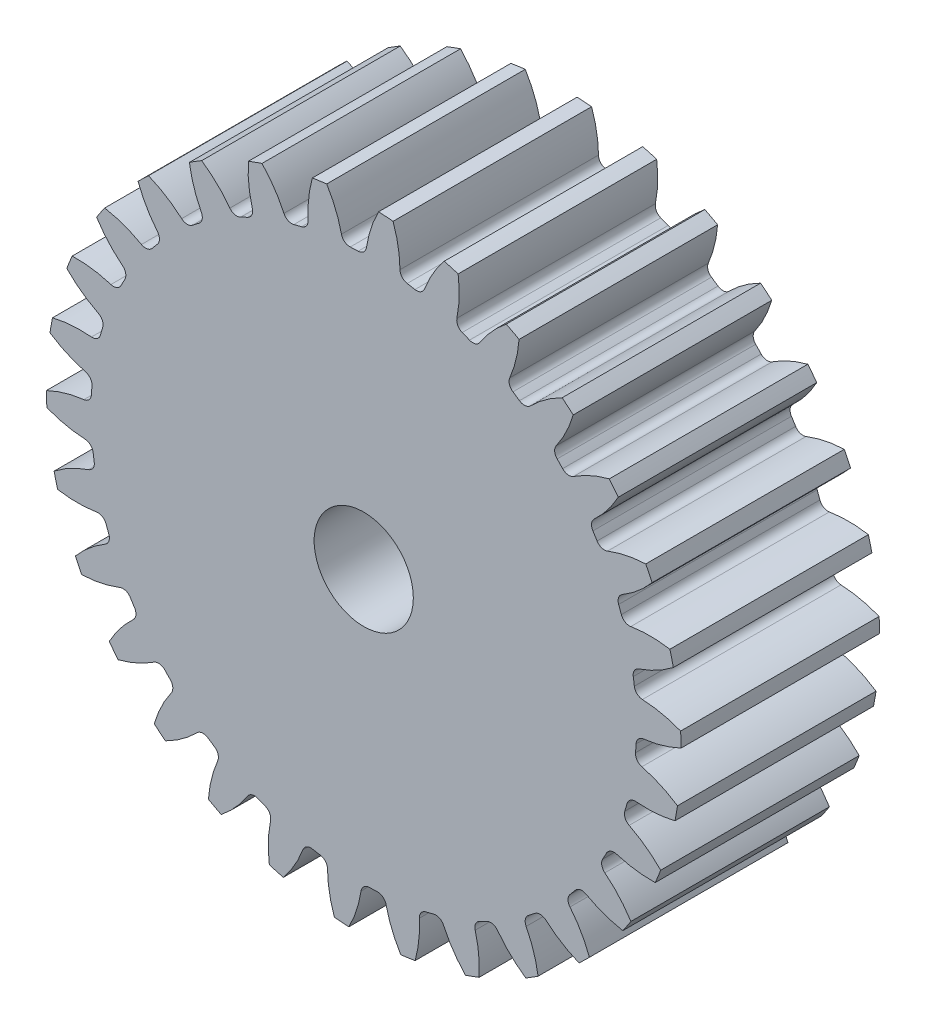
SolidWorks part; units mm, degrees
ref_plane "Front" through (0, 0, 0) normal (0, 0, 1) x (1, 0, 0)
ref_plane "Top" through (0, 0, 0) normal (0, 1, 0) x (1, 0, 0)
ref_plane "Right" through (0, 0, 0) normal (1, 0, 0) x (0, 0, -1)
sketch "Sketch3" plane through (0, 0, 0) normal (0, 0, 1) x (1, 0, 0)
  circle A0 centre (0, 0) radius 16
  dimension "od" = 32
extrude "gearBody" add sketch "Sketch3" along normal blind 10.0076
sketch "Sketch2" plane through (0, 0, 0) normal (0, 0, 1) x (1, 0, 0)
  line L0 (0, 0) -> (13.4168, 5.5574) construction
  line L1 (17.85, -4.7288) -> (0, 0) construction
  line L2 (0, 0) -> (36.3143, 0) construction
  line L3 (14.9989, -0.1803) -> (14.8786, -1.9047) construction
  line L5 (14.9387, -1.0425) -> (0, 0) construction
  line L7 (0, 0) -> (14.5222, 0) construction
  arc A0 (14.5193, -0.2915) -> (14.419, -1.728) centre (0, 0) ccw construction
  arc A1 (15.9988, 0.1948) -> (15.8167, -2.4151) centre (0, 0) ccw construction
  arc A2 (14.9989, -0.1803) -> (14.8786, -1.9047) centre (0, 0) ccw construction
  arc A3 (13.7005, -1.1556) -> (13.7283, -0.7585) centre (0, 0) ccw
  arc A4 (17.85, -4.7288) -> (14.021, -1.609) centre (12.5148, -7.3671) ccw
  arc A5 (17.85, -4.7288) -> (18.3338, 2.2037) centre (0, 0) ccw
  arc A6 (18.3338, 2.2037) -> (14.1086, -0.3541) centre (13.4168, 5.5574) cw
  arc A7 (13.7283, -0.7585) -> (14.1086, -0.3541) centre (14.1587, -0.7823) cw
  arc A8 (14.021, -1.609) -> (13.7005, -1.1556) centre (14.1301, -1.1919) cw
  point P6 (18.3338, 2.2037)
  point P22 (17.85, -4.7288)
  dimension "baseDia" = 29.0444
  dimension "od" = 32
  dimension "pd" = 30
  dimension "rd" = 27.4984
  dimension "rFillet" = 0.4311
  dimension "pointX" = 18.3338
  dimension "pointY" = 2.2037
  dimension "CTT" = 1.7244
  dimension "flankCenterAngle" = 22.5
extrude "toothCut" cut sketch "Sketch2" along normal through all
pattern_circular "CirPattern1" count 30 over 360 about axis through (0, 0, 10.0076) along (0, 0, -1) of "toothCut"
ref_axis "toothSpace" through (0, 0, 0) along (0.9976, -0.0696, 0)
ref_axis "Axis2" through (15.7573, -2.7762, 0) along (-0.9848, 0.1735, 0)
sketch "hub1Dia" plane through (0, 0, 0) normal (0, 0, -1) x (-1, 0, 0)
  circle A0 centre (0, 0) radius 5
  dimension "hub1Dia" = 10
extrude "hub1" add sketch "hub1Dia" along normal blind 5
sketch "hub2Dia" plane through (0, 0, 10.0076) normal (0, 0, 1) x (1, 0, 0)
  circle A0 centre (0, 0) radius 0.5
  dimension "hub2dia" = 1
sketch "boreDia" plane through (0, 0, 0) normal (0, 0, 1) x (1, 0, 0)
  circle A0 centre (0, 0) radius 2.5
  dimension "boreDia" = 5
extrude "bore" cut sketch "boreDia" against normal mid plane 25400
sketch "kwy1sketch" plane through (0, 0, 0) normal (0, 0, 1) x (1, 0, 0)
  line L0 (-5.3271, 0.7479) -> (0, 0) construction
  line L1 (3.5355, 0.0085) -> (3.3965, -0.9818)
  line L2 (3.3965, -0.9818) -> (2.1586, -0.808)
  line L3 (3.5355, 0.0085) -> (2.2977, 0.1823)
  line L4 (2.1586, -0.808) -> (0, 0)
  line L5 (0, 0) -> (2.2977, 0.1823)
  line L6 (0, 0) -> (13.7158, -0.9572) construction
  line L7 (3.466, -0.4866) -> (0, 0) construction
  arc A7 (13.7005, -1.1556) -> (13.7283, -0.7585) centre (0, 0) ccw construction
  point P9 (3.466, -0.4866)
  point P13 (-0.8886, 0.1248)
  dimension "kwy1width" = 1
  dimension "kwy1depth" = 3.5
  dimension "kwy1angle" = 4
  dimension "kwy1Depth2" = 1.25
sketch "kwy2sketch" plane through (0, 0, 0) normal (0, 0, 1) x (1, 0, 0)
  line L0 (13.7158, -0.9572) -> (0, 0) construction
  line L1 (0, 0) -> (-2.9685, -2.2375) construction
  line L2 (2.494, 2.506) -> (3.0959, 1.7075)
  line L3 (3.0959, 1.7075) -> (2.0977, 0.9551)
  line L4 (2.494, 2.506) -> (1.4958, 1.7536)
  line L5 (2.0977, 0.9551) -> (0, 0)
  line L6 (0, 0) -> (1.4958, 1.7536)
  arc A2 (13.7005, -1.1556) -> (13.7283, -0.7585) centre (0, 0) ccw construction
  point P10 (2.7949, 2.1067)
  dimension "kwy2angle" = 41
  dimension "kwy2Width" = 1
  dimension "kwy2depth" = 3.5
  dimension "kwy2Depth2" = 1.25
sketch "kwy3sketch" plane through (0, 0, 0) normal (0, 0, 1) x (1, 0, 0)
  line L0 (13.7158, -0.9572) -> (0, 0) construction
  line L1 (0, 0) -> (-0.3739, -2.6632) construction
  line L2 (-0.0085, 3.5355) -> (0.9818, 3.3965)
  line L3 (0.9818, 3.3965) -> (0.808, 2.1586)
  line L4 (-0.0085, 3.5355) -> (-0.1823, 2.2977)
  line L5 (0.808, 2.1586) -> (0, 0)
  line L6 (-0.1823, 2.2977) -> (0, 0)
  point P10 (0.4866, 3.466)
  dimension "kwy3angle" = 86
  dimension "kwy3depth" = 3.5
  dimension "kwy3width" = 1
  dimension "kwy3Depth2" = 1.25
sketch "kwy4sketch" plane through (0, 0, 0) normal (0, 0, 1) x (1, 0, 0)
  line L0 (13.7158, -0.9572) -> (0, 0) construction
  line L1 (0, 0) -> (1.2657, -1.6792) construction
  line L2 (-1.7075, 3.0959) -> (-2.506, 2.494)
  line L3 (-2.506, 2.494) -> (-1.7536, 1.4958)
  line L4 (-1.7536, 1.4958) -> (0, 0)
  line L5 (-0.9551, 2.0977) -> (0, 0)
  line L6 (-1.7075, 3.0959) -> (-0.9551, 2.0977)
  point P15 (-2.1067, 2.7949)
  dimension "kwy4angle" = 131
  dimension "kwy4depth" = 3.5
  dimension "kwy4width" = 1
  dimension "kwy4Depth2" = 1.25
sketch "kwy5sketch" plane through (0, 0, 0) normal (0, 0, 1) x (1, 0, 0)
  line L0 (13.7158, -0.9572) -> (0, 0) construction
  line L1 (0, 0) -> (1.7884, -0.2511) construction
  line L2 (-3.3965, 0.9818) -> (-3.5355, -0.0085)
  line L3 (-3.5355, -0.0085) -> (-2.2977, -0.1823)
  line L4 (-3.3965, 0.9818) -> (-2.1586, 0.808)
  line L5 (-2.2977, -0.1823) -> (0, 0)
  line L6 (-2.1586, 0.808) -> (0, 0)
  point P10 (-3.466, 0.4866)
  dimension "kwy5width" = 1
  dimension "kwy5depth" = 3.5
  dimension "kwy5angle" = 176
  dimension "kwy5Depth2" = 1.25
sketch "kwy6sketch" plane through (0, 0, 0) normal (0, 0, 1) x (1, 0, 0)
  line L0 (13.7158, -0.9572) -> (0, 0) construction
  line L1 (0, 0) -> (1.441, 1.0862) construction
  line L2 (-3.0959, -1.7075) -> (-2.494, -2.506)
  line L3 (-2.494, -2.506) -> (-1.4958, -1.7536)
  line L4 (-3.0959, -1.7075) -> (-2.0977, -0.9551)
  line L5 (-1.4958, -1.7536) -> (0, 0)
  line L6 (-2.0977, -0.9551) -> (0, 0)
  point P10 (-2.7949, -2.1067)
  dimension "kwy6angle" = 221
  dimension "kwy6width" = 1
  dimension "kwy6depth" = 3.5
  dimension "kwy6Depth2" = 1.25
sketch "kwy7sketch" plane through (0, 0, 0) normal (0, 0, 1) x (1, 0, 0)
  line L0 (13.7158, -0.9572) -> (0, 0) construction
  line L1 (0, 0) -> (0.2811, 2.002) construction
  line L2 (-0.9818, -3.3965) -> (0.0085, -3.5355)
  line L3 (-0.9818, -3.3965) -> (-0.808, -2.1586)
  line L4 (0.0085, -3.5355) -> (0.1823, -2.2977)
  line L5 (-0.808, -2.1586) -> (0, 0)
  line L6 (0.1823, -2.2977) -> (0, 0)
  point P10 (-0.4866, -3.466)
  dimension "kwy7angle" = 86
  dimension "kwy7width" = 1
  dimension "kwy7depth" = 3.5
  dimension "kwy7angle1" = 266
  dimension "kwy7Depth2" = 1.25
sketch "kwy8sketch" plane through (0, 0, 0) normal (0, 0, 1) x (1, 0, 0)
  line L0 (13.7158, -0.9572) -> (0, 0) construction
  line L1 (0, 0) -> (-1.0811, 1.4343) construction
  line L2 (1.7075, -3.0959) -> (2.506, -2.494)
  line L3 (2.506, -2.494) -> (1.7536, -1.4958)
  line L4 (1.7075, -3.0959) -> (0.9551, -2.0977)
  line L5 (1.7536, -1.4958) -> (0, 0)
  line L6 (0.9551, -2.0977) -> (0, 0)
  point P10 (2.1067, -2.7949)
  dimension "kwy8angle" = 311
  dimension "kwy8width" = 1
  dimension "kwy8depth" = 3.5
  dimension "kwy8Depth2" = 1.25
sketch "centerLine" plane through (0, 0, 0) normal (0, 1, 0) x (1, 0, 0)
  line L0 (0, 36.4807) -> (0, -59.6309) construction
ref_plane "CB1plane" through (0, 0, -5) normal (0, 0, -1) x (-1, 0, 0)
sketch "CB1diameter" plane through (0, 0, -5) normal (0, 0, -1) x (-1, 0, 0)
  circle A0 centre (0, 0) radius 0.5
  dimension "CB1diameter" = 1
ref_plane "CB2plane" through (0, 0, 10.0076) normal (0, 0, 1) x (1, 0, 0)
sketch "CB2diameter" plane through (0, 0, 10.0076) normal (0, 0, 1) x (1, 0, 0)
  circle A0 centre (0, 0) radius 0.5
  dimension "CB2diameter" = 1
ref_axis "Axis1" through (0, 0, 50) along (0, 0, -1)
sketch3d "3DSketch1" plane through (0, 0, 0) normal (0, 0, 1) x (1, 0, 0)
